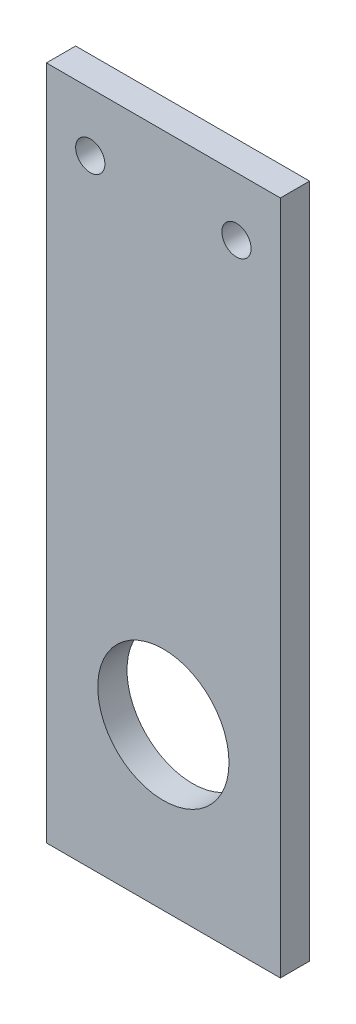
SolidWorks part; units mm, degrees
material "6061-T6 (SS)"
ref_plane "Front Plane" through (0, 0, 0) normal (0, 0, 1) x (1, 0, 0)
ref_plane "Top Plane" through (0, 0, 0) normal (0, 1, 0) x (1, 0, 0)
ref_plane "Right Plane" through (0, 0, 0) normal (1, 0, 0) x (0, 0, -1)
sketch "Sketch1" plane through (0, 0, 0) normal (0, 0, 1) x (1, 0, 0)
  line L0 (-25.4, -146.685) -> (25.4, -146.685)
  line L1 (-25.4, 0) -> (25.4, 0)
  line L2 (-25.4, 0) -> (-25.4, -146.685)
  line L4 (25.4, 0) -> (25.4, -146.685)
  circle A1 centre (0, -130.81) radius 14.2494 construction
  circle A2 centre (0, -111.76) radius 14.2494
  circle A3 centre (0, -92.71) radius 14.2494 construction
  circle A4 centre (0, -73.66) radius 14.2494 construction
  circle A5 centre (-15.875, -12.7) radius 3.175
  circle A6 centre (15.875, -12.7) radius 3.175
  circle A7 centre (0, -48.26) radius 14.2494 construction
  point P18 (0, 0)
  dimension "D6" = 28.4988
  dimension "D7" = 6.35
  dimension "D8" = 25.4
  dimension "D11" = 111.76
  dimension "D16" = 9.525
  dimension "D1" = 50.8
  dimension "D3" = 15.875
  dimension "D4" = 25.4
  dimension "D9" = 19.05
  dimension "D10" = 19.05
  dimension "D12" = 19.05
  dimension "D15" = 9.525
  dimension "D17" = 12.7
  dimension "D18" = 12.7
  dimension "D19" = 25.4
  dimension "D20" = 25.4
  dimension "D21" = 25.4
extrude "Boss-Extrude3" add sketch "Sketch1" along normal blind 6.35
chamfer "Chamfer1" [suppressed] distance 4.0894 angle 41
chamfer "Chamfer2" [suppressed] distance 4.0894 angle 41
